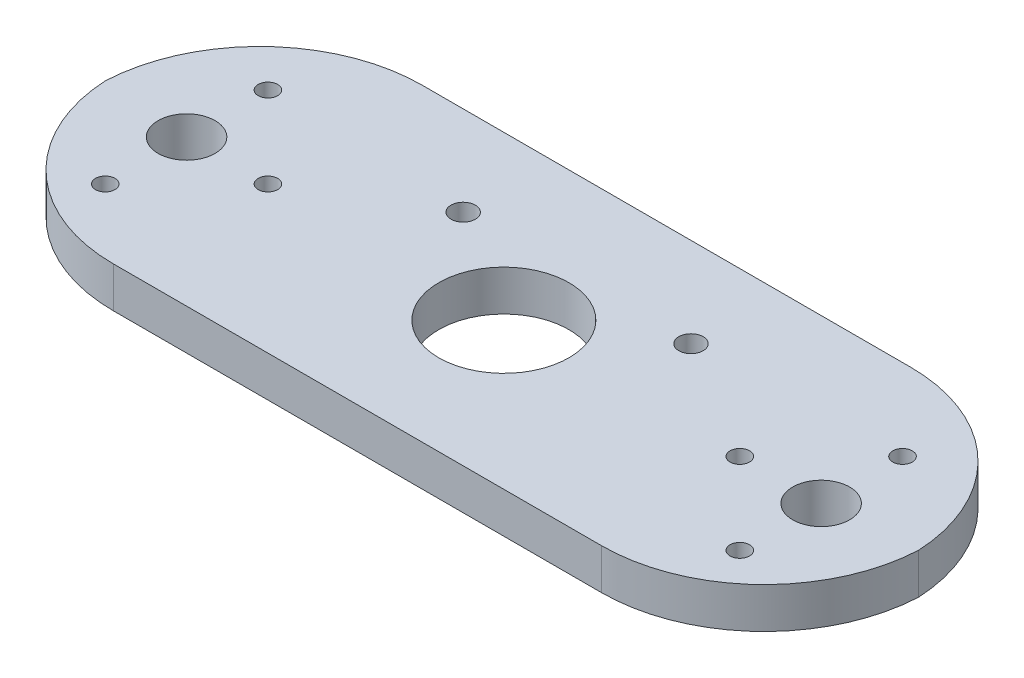
SolidWorks part; units mm, degrees
ref_plane "前视基准面" through (0, 0, 0) normal (0, 0, 1) x (1, 0, 0)
ref_plane "上视基准面" through (0, 0, 0) normal (0, 1, 0) x (1, 0, 0)
ref_plane "右视基准面" through (0, 0, 0) normal (1, 0, 0) x (0, 0, -1)
sketch "草图1" plane through (0, 0, 0) normal (0, 1, 0) x (1, 0, 0)
  line L1 (-50, 20) -> (50, 20)
  line L2 (-50, 20) -> (-50, -18)
  line L3 (-50, -18) -> (50, -18)
  line L4 (50, 20) -> (50, -18)
  line L5 (0, -18) -> (0, 20) construction
  line L6 (-50, 0) -> (50, 0) construction
  circle A0 centre (0, 0) radius 8
  circle A1 centre (39, 0) radius 3.5
  circle A2 centre (-39, 0) radius 3.5
  point P0 (0, 0)
  dimension "D3" = 16
  dimension "D4" = 7
  dimension "D1" = 38
  dimension "D2" = 100
  dimension "D5" = 78
  dimension "D6" = 20
extrude "凸台-拉伸1" add sketch "草图1" along normal blind 5
fillet "圆角1" radius 20 4 edges at (-50, 2.5, -20) (-50, 2.5, 18) (50, 2.5, -20) (50, 2.5, 18)
hole_wizard "大小mm Transitional 暗销孔1" positions "草图2" profile "草图3" hole size "Ø3.0" standard "GB" end condition through all
sketch "草图2" plane through (0, 5, 0) normal (0, 1, 0) x (1, 0, 0)
  line L0 (0, -4.1879) -> (0, 16.2588) construction
  line L2 (16.4412, 0) -> (-18.8394, 0) construction
  point P0 (14, 9)
  point P3 (-14, 9)
  dimension "D1" = 9
  dimension "D2" = 14
sketch "草图3" plane through (14, 5, -9) normal (1, 0, 0) x (0, 0, 1)
  line L0 (0, 0) -> (0, 5)
  line L1 (0, 5) -> (1.5, 5)
  line L2 (1.5, 5) -> (1.5, 0)
  line L5 (1.5, 0) -> (0, 0)
  line L11 (0, -6.35) -> (0, 107.95) construction
  dimension "通孔孔直径" = 3
  dimension "通孔孔深度" = 5
hole_wizard "M2 间隙孔1" positions "草图4" profile "草图5" hole size "M2" standard "GB" end condition through all
sketch "草图4" plane through (0, 5, 0) normal (0, 1, 0) x (0, 0, 1)
  point P0 (-10, 39)
  point P1 (10, 39)
  point P2 (0, 29)
sketch "草图5" plane through (39, 5, -10) normal (1, 0, 0) x (0, 0, 1)
  line L0 (0, 0) -> (0, 5)
  line L1 (0, 5) -> (1.2, 5)
  line L2 (1.2, 5) -> (1.2, 0)
  line L3 (1.2, 0) -> (0, 0)
  line L4 (0, -6.35) -> (0, 107.95) construction
  dimension "通孔孔直径" = 2.4
  dimension "通孔孔深度" = 5
mirror "镜向1" about plane through (0, 0, 0) normal (1, 0, 0) of "M2 间隙孔1"
